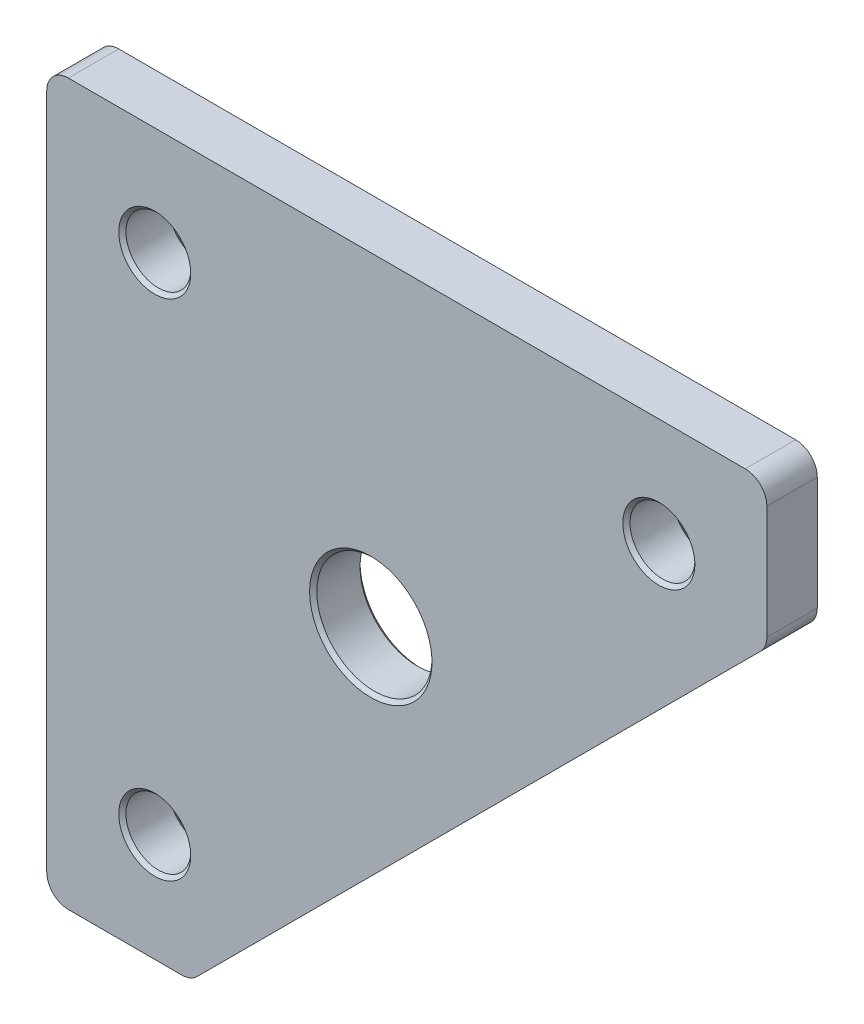
SolidWorks part; units mm, degrees
ref_plane "Front Plane" through (0, 0, 0) normal (0, 0, 1) x (1, 0, 0)
ref_plane "Top Plane" through (0, 0, 0) normal (0, 1, 0) x (1, 0, 0)
ref_plane "Right Plane" through (0, 0, 0) normal (1, 0, 0) x (0, 0, -1)
ref_plane "Plane1" through (0, 0, 0) normal (0, 0, -1) x (-1, 0, 0)
sketch "Sketch1" plane through (0, 0, 0) normal (0, 0, -1) x (-1, 0, 0)
  line L0 (0, 0) -> (-100, 0)
  line L1 (-100, 0) -> (-100, -20)
  line L2 (-100, -20) -> (-20, -100)
  line L3 (-20, -100) -> (0, -100)
  line L4 (0, -100) -> (0, 0)
extrude "Boss-Extrude1" add sketch "Sketch1" against normal blind 7
hole_wizard "Ø9.0 (9) Diameter Hole1" positions "Sketch3" profile "Sketch2" hole size "Ø9.0" standard "ANSI Metric"
sketch "Sketch3" plane through (0, 0, 7) normal (0, 0, 1) x (1, 0, 0)
  point P0 (85, -15)
  point P1 (15, -15)
sketch "Sketch2" plane through (85, -15, 7) normal (1, 0, 0) x (0, -1, 0)
  line L0 (0, 0) -> (0, 7)
  line L1 (0, 7) -> (4.5, 7)
  line L2 (4.5, 7) -> (4.5, 0)
  line L5 (4.5, 0) -> (0, 0)
  line L11 (0, -6.35) -> (0, 107.95) construction
  dimension "Thru Hole Dia." = 9
  dimension "Thru Hole Depth" = 7
hole_wizard "Ø16.0 (16) Diameter Hole1" positions "Sketch5" profile "Sketch4" hole size "Ø16.0" standard "ANSI Metric"
sketch "Sketch5" plane through (0, 0, 7) normal (0, 0, 1) x (1, 0, 0)
  point P0 (45, -45)
sketch "Sketch4" plane through (45, -45, 7) normal (1, 0, 0) x (0, -1, 0)
  line L0 (0, 0) -> (0, 7)
  line L1 (0, 7) -> (8, 7)
  line L2 (8, 7) -> (8, 0)
  line L5 (8, 0) -> (0, 0)
  line L11 (0, -6.35) -> (0, 107.95) construction
  dimension "Thru Hole Dia." = 16
  dimension "Thru Hole Depth" = 7
hole_wizard "Ø9.0 (9) Diameter Hole2" positions "Sketch7" profile "Sketch6" hole size "Ø9.0" standard "ANSI Metric"
sketch "Sketch7" plane through (0, 0, 0) normal (0, 0, -1) x (-1, 0, 0)
  point P0 (-15, -85)
sketch "Sketch6" plane through (15, -85, 0) normal (1, 0, 0) x (0, 1, 0)
  line L0 (0, 0) -> (0, 7)
  line L1 (0, 7) -> (4.5, 7)
  line L2 (4.5, 7) -> (4.5, 0)
  line L5 (4.5, 0) -> (0, 0)
  line L11 (0, -6.35) -> (0, 107.95) construction
  dimension "Thru Hole Dia." = 9
  dimension "Thru Hole Depth" = 7
chamfer "Chamfer1" distance 0.5 angle 45 8 edges at (89.5, -15, 0) (10.5, -85, 7) (53, -45, 0) (10.5, -85, 0) (19.5, -15, 0) (19.5, -15, 7) (53, -45, 7) (89.5, -15, 7)
fillet "Fillet1" radius 3 5 edges at (0, -100, 3.5) (0, 0, 3.5) (20, -100, 3.5) (100, -20, 3.5) (100, 0, 3.5) tangent propagation no
